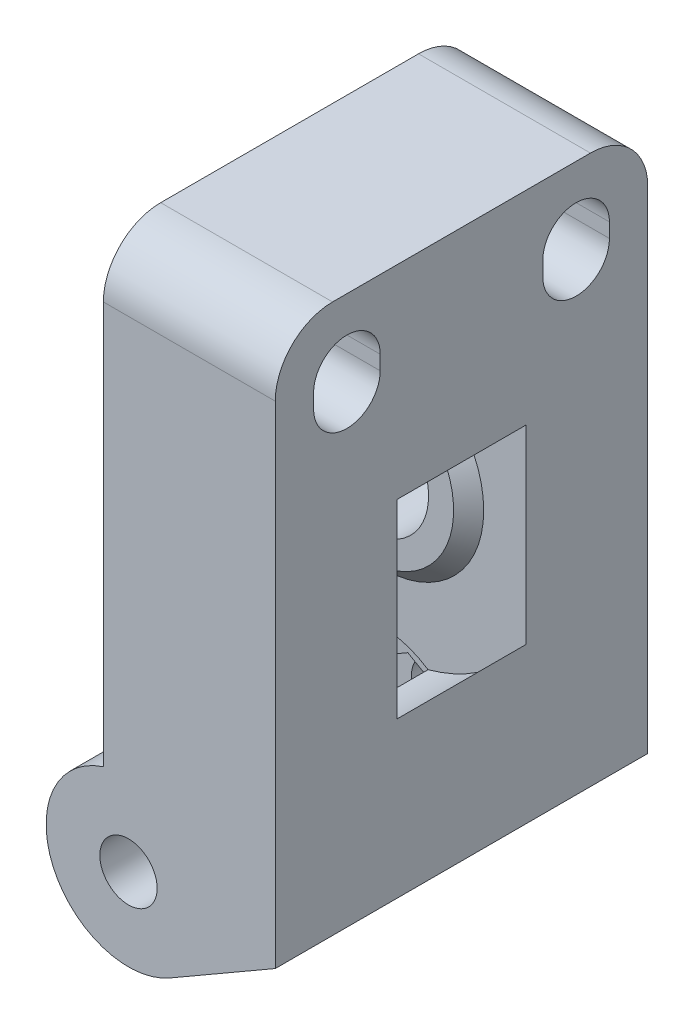
SolidWorks part; units mm, degrees
material "ABS"
ref_plane "Front Plane" through (0, 0, 0) normal (0, 0, 1) x (1, 0, 0)
ref_plane "Top Plane" through (0, 0, 0) normal (0, 1, 0) x (1, 0, 0)
ref_plane "Right Plane" through (0, 0, 0) normal (1, 0, 0) x (0, 0, -1)
sketch "Sketch1" plane through (0, 0, 0) normal (0, 0, 1) x (1, 0, 0)
  line L0 (-1.7542, 5.4759) -> (-1.7542, 37.5759)
  line L1 (-1.7542, 37.5759) -> (10.2458, 37.5759)
  line L2 (10.2458, 37.5759) -> (10.2458, -0.7241)
  line L3 (10.2458, -0.7241) -> (2.875, -4.9796)
  arc A0 (2.875, -4.9796) -> (-1.7542, 5.4759) centre (0, 0) cw
  dimension "D3" = 5.75
  dimension "D1" = 12
  dimension "D2" = 120
  dimension "D4" = 32.1
  dimension "D5" = 38.3
extrude "Boss-Extrude1" add sketch "Sketch1" along normal blind 13 and the other way blind 13
sketch "Sketch2" plane through (0, 0, 0) normal (0, 0, 1) x (1, 0, 0)
  line L0 (8.2444, -1.8796) -> (5.3694, 3.1)
  line L1 (2.875, -4.9796) -> (10.2458, -0.7241) construction
  line L2 (-1.7542, 37.5759) -> (-1.7542, 5.4759) construction
  line L3 (8.2444, -1.8796) -> (8.2444, -5.75)
  line L4 (8.2444, -5.75) -> (-5.75, -5.75)
  line L5 (-5.75, -5.75) -> (-5.75, 5.9467)
  line L6 (-5.75, 5.9467) -> (-1.7542, 5.9467)
  arc A0 (5.3694, 3.1) -> (-1.7542, 5.9467) centre (0, 0) ccw
  arc A1 (-1.7542, 5.4759) -> (2.875, -4.9796) centre (0, 0) ccw construction
  dimension "D1" = 6.2
extrude "Cut-Extrude1" cut sketch "Sketch2" against normal blind 6.5 and the other way blind 6.5
sketch "Sketch3" plane through (0, 0, 0) normal (0, 0, 1) x (1, 0, 0)
  line L0 (10.2458, 37.5759) -> (-1.7542, 37.5759) construction
  line L1 (10.2458, -0.7241) -> (10.2458, 37.5759) construction
  circle A0 centre (0.2458, 16.7509) radius 12
  dimension "D1" = 24
  dimension "D3" = 10
  dimension "D2" = 20.825
extrude "Cut-Extrude3" cut sketch "Sketch3" against normal blind 4.5 and the other way blind 4.5
sketch "Sketch4" plane through (0, 0, 0) normal (0, 0, 1) x (1, 0, 0)
  line L0 (10.2458, -0.7241) -> (10.2458, 37.5759) construction
  line L1 (10.2458, 37.5759) -> (-1.7542, 37.5759) construction
  circle A0 centre (0.2458, 16.7509) radius 4.25
  dimension "D2" = 8.5
  dimension "D1" = 10
  dimension "D3" = 20.825
extrude "Cut-Extrude4" cut sketch "Sketch4" against normal blind 10 and the other way blind 10
sketch "Sketch5" plane through (0, 0, 13) normal (0, 0, 1) x (1, 0, 0)
  circle A0 centre (0, 0) radius 2
  dimension "D1" = 4
extrude "Cut-Extrude5" cut sketch "Sketch5" against normal through all
sketch3d "3DSketch3"
  line L0 (10.2458, 23.3841, -4.5) -> (10.2458, 10.1176, -4.5) construction
  line L1 (-1.7542, 13.0009, -10) -> (-1.7542, 20.5009, -10) construction
  line L2 (10.2458, 23.3841, 4.5) -> (10.2458, 10.1176, 4.5) construction
  line L3 (4.4958, 16.7509, 4.5) -> (7.2958, 16.7509, 4.5)
  line L4 (7.2958, 16.7509, 4.5) -> (6.2458, 16.7509, 3.45)
  line L5 (6.2458, 16.7509, 3.45) -> (4.4958, 16.7509, 3.45)
  line L6 (4.4958, 16.7509, 3.45) -> (4.4958, 16.7509, 4.5)
  arc A1 (-1.7542, 20.5009, 4.5) -> (-1.7542, 13.0009, 4.5) centre (0.2458, 16.7509, 4.5) ccw construction
  point P2 (10.2458, 16.7509, -4.5)
  point P9 (-1.7542, 16.7509, -10)
  point P12 (10.2458, 16.7509, 4.5)
  point P16 (0.2458, 16.7509, 0.25)
  dimension "D1" = 45
  dimension "D2" = 1.75
  dimension "D3" = 1.05
sketch "Sketch8" plane through (0, 0, 4.5) normal (0, 0, -1) x (-1, 0, 0)
  circle A0 centre (-0.2458, 16.7509) radius 4.25
  arc A1 (1.7542, 20.5009) -> (1.7542, 13.0009) centre (-0.2458, 16.7509) ccw construction
sweep "Sweep4" add profiles "3DSketch3" path "Sketch8"
mirror "Mirror10" about plane through (0, 0, 0) normal (0, 0, 1) of "Sweep4"
sketch "Sketch9" plane through (0, 0, 4.5) normal (0, 0, -1) x (-1, 0, 0)
  line L1 (1.7542, 23.5112) -> (6.8042, 23.5112)
  line L2 (1.7542, 23.5112) -> (1.7542, 9.9905)
  line L3 (1.7542, 9.9905) -> (6.8042, 9.9905)
  line L4 (6.8042, 23.5112) -> (6.8042, 9.9905)
  arc A0 (1.7542, 9.9905) -> (1.7542, 23.5112) centre (-0.2458, 16.7509) ccw construction
extrude "Cut-Extrude8" cut sketch "Sketch9" along normal through all
sketch "Sketch10" plane through (-1.7542, 0, 0) normal (-1, 0, 0) x (0, 0, 1)
  line L0 (-8, 32.7509) -> (-8, 31.7509) construction
  line L1 (-5.675, 32.7509) -> (-5.675, 31.7509)
  line L2 (-10.325, 32.7509) -> (-10.325, 31.7509)
  line L3 (-13, 37.5759) -> (-13, 5.4759) construction
  line L4 (-13, 37.5759) -> (13, 37.5759) construction
  line L5 (0, 37.5759) -> (0, 28.583) construction
  line L6 (-4.5, 28.583) -> (4.5, 28.583) construction
  line L7 (8, 32.7509) -> (8, 31.7509) construction
  line L8 (5.675, 32.7509) -> (5.675, 31.7509)
  line L9 (10.325, 32.7509) -> (10.325, 31.7509)
  arc A0 (-5.675, 32.7509) -> (-10.325, 32.7509) centre (-8, 32.7509) ccw
  arc A1 (-10.325, 31.7509) -> (-5.675, 31.7509) centre (-8, 31.7509) ccw
  arc A2 (5.675, 32.7509) -> (10.325, 32.7509) centre (8, 32.7509) cw
  arc A3 (10.325, 31.7509) -> (5.675, 31.7509) centre (8, 31.7509) cw
  point P2 (-8, 32.2509)
  point P17 (8, 32.2509)
  dimension "D1" = 4.65
  dimension "D2" = 1
  dimension "D3" = 5
  dimension "D4" = 5.325
extrude "Cut-Extrude9" cut sketch "Sketch10" against normal through all
fillet "Fillet1" radius 4 2 edges at (4.2458, 37.5759, 13) (4.2458, 37.5759, -13)
sketch "Sketch11" plane through (0, 0, -6.5) normal (0, 0, 1) x (1, 0, 0)
  line L1 (0, 3.5) -> (-3.0311, 1.75)
  line L2 (-3.0311, 1.75) -> (-3.0311, -1.75)
  line L3 (-3.0311, -1.75) -> (0, -3.5)
  line L4 (0, -3.5) -> (3.0311, -1.75)
  line L5 (3.0311, -1.75) -> (3.0311, 1.75)
  line L6 (3.0311, 1.75) -> (0, 3.5)
  circle A0 centre (0, 0) radius 3.0311 construction
  dimension "D1" = 3.5
extrude "Cut-Extrude10" cut sketch "Sketch11" against normal blind 2.25
